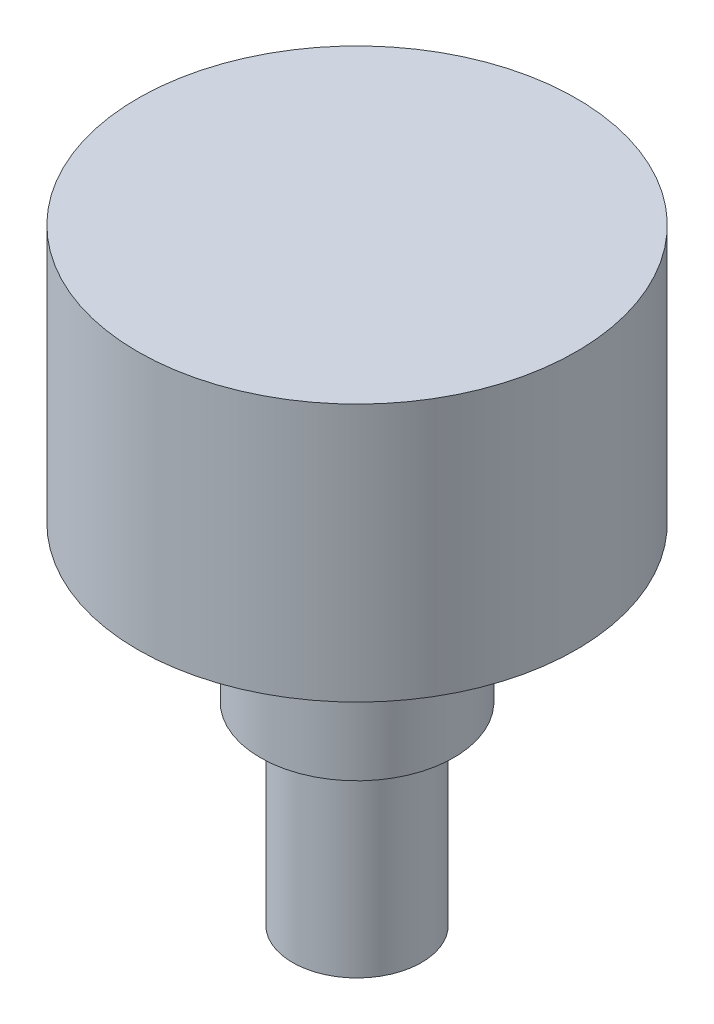
SolidWorks part; units mm, degrees
material "Nylon 101"
ref_plane "Front Plane" through (0, 0, 0) normal (0, 0, 1) x (1, 0, 0)
ref_plane "Top Plane" through (0, 0, 0) normal (0, 1, 0) x (1, 0, 0)
ref_plane "Right Plane" through (0, 0, 0) normal (1, 0, 0) x (0, 0, -1)
sketch "Sketch1" plane through (0, 0, 0) normal (0, 1, 0) x (1, 0, 0)
  circle A0 centre (0, 0) radius 10.795
  dimension "D1" = 21.59
extrude "Boss-Extrude1" add sketch "Sketch1" along normal blind 12.7
sketch "Sketch2" plane through (0, 0, 0) normal (0, -1, 0) x (1, 0, 0)
  circle A0 centre (0, 0) radius 4.7625
  dimension "D1" = 9.525
extrude "Boss-Extrude2" add sketch "Sketch2" along normal blind 17.145
sketch "Sketch3" plane through (0, -17.145, 0) normal (0, -1, 0) x (1, 0, 0)
  circle A0 centre (0, 0) radius 3.175
  dimension "D1" = 6.35
extrude "Cut-Extrude1" cut sketch "Sketch3" against normal blind 9.525 flip side to cut
ref_axis "Axis1" through (0, -21.6338, 0) along (0, 1, 0)
